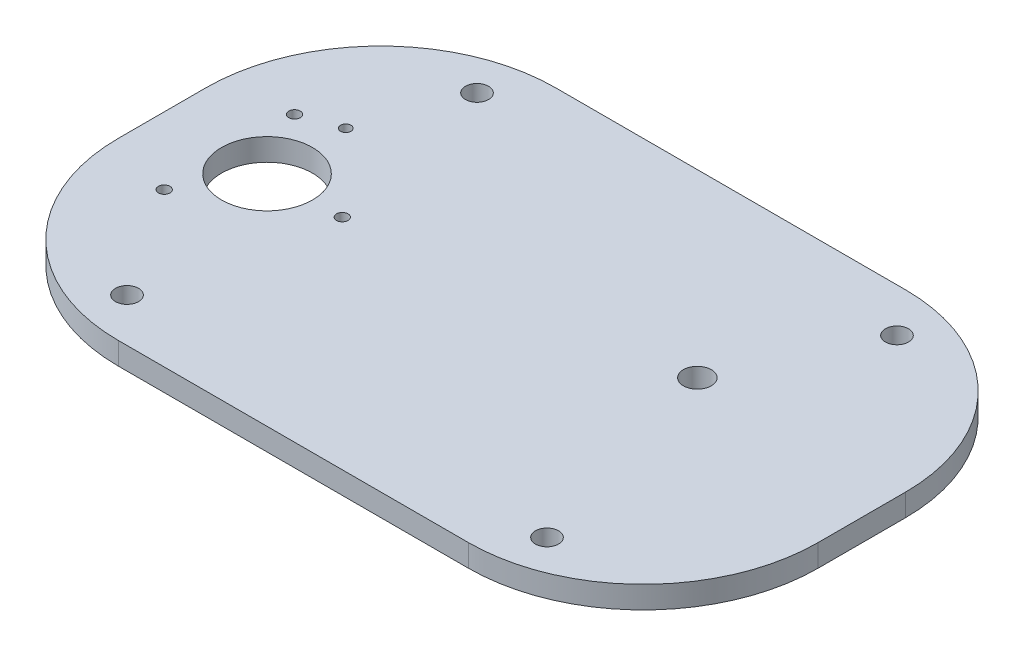
SolidWorks part; units mm, degrees
ref_plane "Front Plane" through (0, 0, 0) normal (0, 0, 1) x (1, 0, 0)
ref_plane "Top Plane" through (0, 0, 0) normal (0, 1, 0) x (1, 0, 0)
ref_plane "Right Plane" through (0, 0, 0) normal (1, 0, 0) x (0, 0, -1)
sketch "Sketch2" plane through (0, 0, 0) normal (0, 1, 0) x (1, 0, 0)
  line L1 (-100, -62.5) -> (100, -62.5)
  line L2 (-100, -62.5) -> (-100, 62.5)
  line L3 (-100, 62.5) -> (100, 62.5)
  line L4 (100, -62.5) -> (100, 62.5)
  line L5 (-100, -62.5) -> (100, 62.5) construction
  line L6 (-100, 62.5) -> (100, -62.5) construction
  arc A2 (-40.3, 0) -> (-99.7, 0) centre (-70, 0) ccw
  arc A3 (-99.7, 0) -> (-40.3, 0) centre (-70, 0) ccw
  arc A4 (-40.3, 0) -> (-99.7, 0) centre (-70, 0) ccw
  arc A5 (-99.7, 0) -> (-40.3, 0) centre (-70, 0) ccw
  arc A10 (-68.5, 22.5) -> (-71.5, 22.5) centre (-70, 22.5) ccw
  arc A11 (-71.5, 22.5) -> (-68.5, 22.5) centre (-70, 22.5) ccw
  arc A12 (-68.5, 22.5) -> (-71.5, 22.5) centre (-70, 22.5) ccw
  arc A13 (-71.5, 22.5) -> (-68.5, 22.5) centre (-70, 22.5) ccw
  arc A14 (-79.925, -17.1906) -> (-81.575, -20.0485) centre (-80.75, -18.6195) ccw
  arc A15 (-81.575, -20.0485) -> (-79.925, -17.1906) centre (-80.75, -18.6195) ccw
  arc A16 (-79.925, -17.1906) -> (-81.575, -20.0485) centre (-80.75, -18.6195) ccw
  arc A17 (-81.575, -20.0485) -> (-79.925, -17.1906) centre (-80.75, -18.6195) ccw
  arc A18 (-79.925, 17.1906) -> (-81.575, 20.0485) centre (-80.75, 18.6195) ccw
  arc A19 (-81.575, 20.0485) -> (-79.925, 17.1906) centre (-80.75, 18.6195) ccw
  arc A20 (-79.925, 17.1906) -> (-81.575, 20.0485) centre (-80.75, 18.6195) ccw
  arc A21 (-81.575, 20.0485) -> (-79.925, 17.1906) centre (-80.75, 18.6195) ccw
  arc A22 (-50.15, 0) -> (-46.85, 0) centre (-48.5, 0) ccw
  arc A23 (-46.85, 0) -> (-50.15, 0) centre (-48.5, 0) ccw
  arc A24 (-50.15, 0) -> (-46.85, 0) centre (-48.5, 0) ccw
  arc A25 (-46.85, 0) -> (-50.15, 0) centre (-48.5, 0) ccw
  arc A26 (-83, 0) -> (-57, 0) centre (-70, 0) ccw
  arc A27 (-57, 0) -> (-83, 0) centre (-70, 0) ccw
  arc A28 (-83, 0) -> (-57, 0) centre (-70, 0) ccw
  arc A29 (-57, 0) -> (-83, 0) centre (-70, 0) ccw
  circle A36 centre (41.9609, 11) radius 4
  circle A37 centre (41.9609, 11) radius 10.4365
  circle A38 centre (41.9609, 11) radius 10.4365
  point P0 (0, 0)
  dimension "D10" = 8
  dimension "D1" = 200
  dimension "D2" = 125
  dimension "D3" = 0
  dimension "D4" = 0
  dimension "D5" = 0
  dimension "D6" = 0
  dimension "D7" = 0
  dimension "D8" = 0
  dimension "D9" = 0
extrude "Boss-Extrude1" add sketch "Sketch2" along normal blind 6.35 contours A5 L2 L1 L4 L3 A4 | A4 A5 A29 A28 A25 A24 A21 A20 A17 A16 A13 A12 | A38 A36 region at (8.207, 0, 0.172) region at (-70, 0, 28.86) region at (31.8196, 0, -11)
fillet "Fillet1" radius 50 4 edges at (100, 3.175, 62.5) (100, 3.175, -62.5) (-100, 3.175, -62.5) (-100, 3.175, 62.5)
hole_wizard "M6 Clearance Hole1" positions "Sketch3" profile "Sketch4" hole size "M6" standard "ANSI Metric"
sketch "Sketch3" plane through (0, 6.35, 0) normal (0, 1, 0) x (1, 0, 0)
  line L1 (-60, -50) -> (60, -50)
  line L2 (-60, -50) -> (-60, 50)
  line L3 (-60, 50) -> (60, 50)
  line L4 (60, -50) -> (60, 50)
  line L5 (-60, -50) -> (60, 50) construction
  line L6 (-60, 50) -> (60, -50) construction
  point P2 (60, 50)
  point P111 (-60, -50)
  point P112 (-60, 50)
  point P113 (60, -50)
  dimension "D1" = 120
  dimension "D2" = 100
  dimension "D3" = 60
  dimension "D4" = 50
sketch "Sketch4" plane through (60, 6.35, -50) normal (1, 0, 0) x (0, 0, 1)
  line L0 (0, 0) -> (0, 16.9828)
  line L1 (0, 16.9828) -> (3.3, 15)
  line L2 (3.3, 15) -> (3.3, 0)
  line L5 (3.3, 0) -> (0, 0)
  line L10 (0, 16.9828) -> (-3.3, 15) construction
  line L11 (0, -6.35) -> (0, 107.95) construction
  dimension "Hole Dia." = 6.6
  dimension "Hole Depth" = 15
  dimension "Drill Angle" = 118
